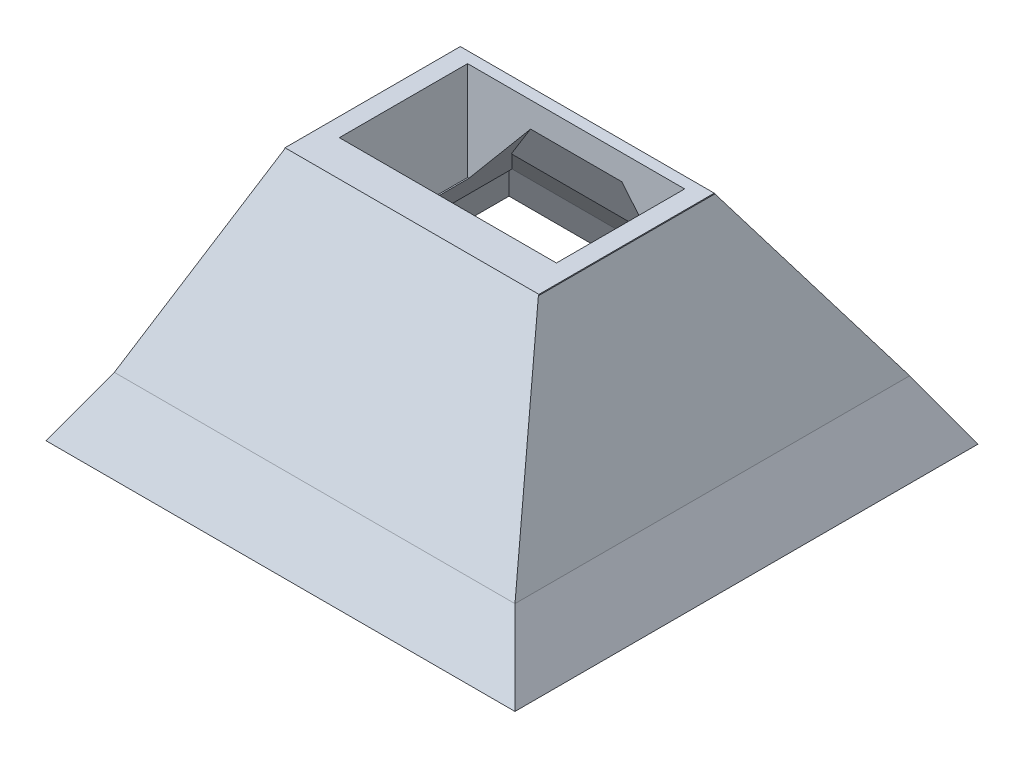
SolidWorks part; units mm, degrees
ref_plane "Front Plane" through (0, 0, 0) normal (0, 0, 1) x (1, 0, 0)
ref_plane "Top Plane" through (0, 0, 0) normal (0, 1, 0) x (1, 0, 0)
ref_plane "Right Plane" through (0, 0, 0) normal (1, 0, 0) x (0, 0, -1)
sketch "Sketch1" plane through (0, 0, 0) normal (0, 1, 0) x (1, 0, 0)
  line L1 (-20, -20) -> (20, -20)
  line L2 (-20, -20) -> (-20, 20)
  line L3 (-20, 20) -> (20, 20)
  line L4 (20, -20) -> (20, 20)
  line L5 (-20, -20) -> (20, 20) construction
  line L6 (-20, 20) -> (20, -20) construction
  point P0 (0, 0)
  dimension "D1" = 40
  dimension "D2" = 40
extrude "Boss-Extrude1" add sketch "Sketch1" along normal blind 8.5 draft 40
sketch "Sketch2" plane through (0, 0, 0) normal (0, -1, 0) x (1, 0, 0)
  line L0 (-20, 20) -> (20, 20) construction
  line L1 (-18, -18) -> (18, -18)
  line L2 (-18, -18) -> (-18, 18)
  line L3 (-18, 18) -> (18, 18)
  line L4 (18, -18) -> (18, 18)
  line L5 (-18, -18) -> (18, 18) construction
  line L6 (-18, 18) -> (18, -18) construction
  line L7 (20, 20) -> (20, -20) construction
  point P0 (0, 0)
  dimension "D1" = 2
  dimension "D2" = 2
extrude "Cut-Extrude1" cut sketch "Sketch2" against normal blind 15 draft 40
sketch "Sketch4" plane through (0, 8.5, 0) normal (0, 1, 0) x (1, 0, 0)
  line L1 (-12.8677, -12.8677) -> (12.8677, -12.8677)
  line L2 (-12.8677, -12.8677) -> (-12.8677, 12.8677)
  line L3 (-12.8677, 12.8677) -> (12.8677, 12.8677)
  line L4 (12.8677, -12.8677) -> (12.8677, 12.8677)
  line L5 (-12.8677, -12.8677) -> (12.8677, 12.8677) construction
  line L6 (-12.8677, 12.8677) -> (12.8677, -12.8677) construction
  point P1 (0, 0)
extrude "Boss-Extrude3" add sketch "Sketch4" along normal blind 10
sketch "Sketch5" plane through (0, 8.5, 0) normal (0, -1, 0) x (1, 0, 0)
  line L1 (-11, -6.5) -> (11, -6.5)
  line L2 (-11, -6.5) -> (-11, 6.5)
  line L3 (-11, 6.5) -> (11, 6.5)
  line L4 (11, -6.5) -> (11, 6.5)
  line L5 (-11, -6.5) -> (11, 6.5) construction
  line L6 (-11, 6.5) -> (11, -6.5) construction
  point P1 (0, 0)
  dimension "D1" = 22
  dimension "D2" = 13
extrude "Cut-Extrude2" cut sketch "Sketch5" against normal through all
chamfer "Chamfer2" distance 12 angle 18 4 edges at (12.8677, 8.5, 0) (-12.8677, 8.5, 0) (0, 8.5, 12.8677) (0, 8.5, -12.8677)
sketch "Sketch7" plane through (0, 0, 0) normal (1, 0, 0) x (0, 0, -1)
  line L2 (22, 0) -> (-22, 0) construction
  line L3 (-20, 0) -> (-24.7859, 0)
  line L4 (-24.7859, 0) -> (-24.7859, 18.533)
  line L7 (-10.14, 18.5) -> (-20, 0)
  line L8 (-12.8677, 18.5) -> (12.8677, 18.5) construction
  line L9 (-10.14, 18.5) -> (-24.7859, 18.533)
  dimension "D1" = 3.64
  dimension "D2" = 2
extrude "Cut-Extrude3" cut sketch "Sketch7" against normal through all both and the other way through all
chamfer "Chamfer3" distance 4.3 angle 60 2 edges at (0, 8.5, -6.5) (0, 8.5, 6.5)
sketch "Sketch8" plane through (0, 0, 0) normal (1, 0, 0) x (0, 0, -1)
  line L0 (7.63, 18.5) -> (12.8677, 18.5)
  line L1 (-10.14, 18.5) -> (12.8677, 18.5) construction
  line L2 (12.8677, 18.5) -> (21.1602, 0)
  line L3 (22.3314, 0) -> (-22.3314, 0) construction
  line L4 (21.1602, 0) -> (20, 0)
  line L5 (20, 0) -> (7.63, 18.5)
  dimension "D1" = 1.13
  dimension "D2" = 2
  dimension "D3" = 5.2377
extrude "Cut-Extrude4" cut sketch "Sketch8" against normal through all both and the other way through all
sketch "Sketch9" plane through (0, 0, 0) normal (0, -1, 0) x (1, 0, 0)
  line L1 (-20.3013, -20) -> (20.3013, -20)
  line L2 (-20.3013, -20) -> (-20.3013, 20)
  line L3 (-20.3013, 20) -> (20.3013, 20)
  line L4 (20.3013, -20) -> (20.3013, 20)
  line L5 (-20.3013, -20) -> (20.3013, 20) construction
  line L6 (-20.3013, 20) -> (20.3013, -20) construction
  point P0 (0, 0)
extrude "Boss-Extrude4" add sketch "Sketch9" along normal blind 6 draft 30 draft outward yes
sketch "Sketch10" plane through (0, 0, 0) normal (0, 1, 0) x (1, 0, 0)
  line L0 (-20.3013, 20) -> (20.3013, 20) construction
  line L1 (-18.3013, -18) -> (18.3013, -18)
  line L2 (-18.3013, -18) -> (-18.3013, 18)
  line L3 (-18.3013, 18) -> (18.3013, 18)
  line L4 (18.3013, -18) -> (18.3013, 18)
  line L5 (-18.3013, -18) -> (18.3013, 18) construction
  line L6 (-18.3013, 18) -> (18.3013, -18) construction
  line L7 (20.3013, 20) -> (20.3013, -20) construction
  point P0 (0, 0)
  dimension "D1" = 2
  dimension "D2" = 2
extrude "Cut-Extrude5" cut sketch "Sketch10" against normal blind 10 draft 30 draft outward yes
